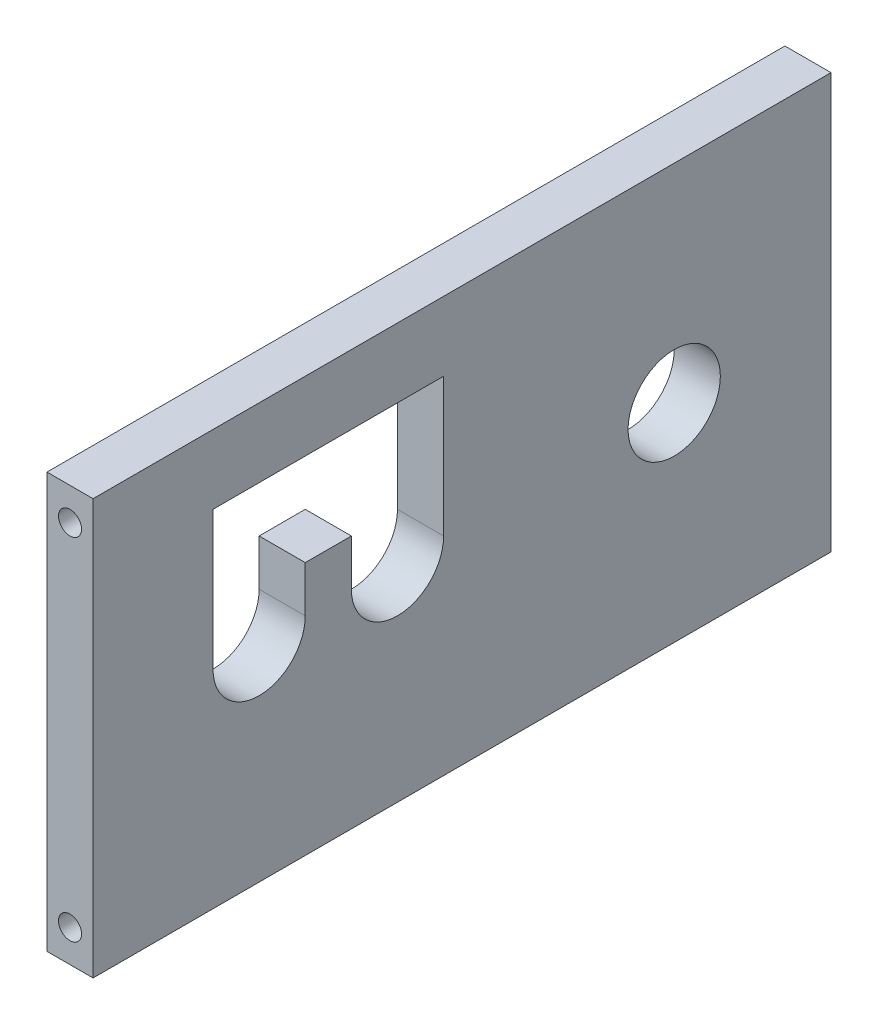
SolidWorks part; units mm, degrees
ref_plane "前视基准面" through (0, 0, 0) normal (0, 0, 1) x (1, 0, 0)
ref_plane "上视基准面" through (0, 0, 0) normal (0, 1, 0) x (1, 0, 0)
ref_plane "右视基准面" through (0, 0, 0) normal (1, 0, 0) x (0, 0, -1)
sketch "草图2" plane through (0, 0, 0) normal (1, 0, 0) x (0, 0, -1)
  line L1 (-40, 22.5) -> (40, 22.5)
  line L2 (-40, 22.5) -> (-40, -22.5)
  line L3 (-40, -22.5) -> (40, -22.5)
  line L4 (40, 22.5) -> (40, -22.5)
  line L5 (0, -22.5) -> (0, 22.5) construction
  line L6 (-40, 0) -> (40, 0) construction
  circle A0 centre (-10, 0) radius 8.7762
  circle A1 centre (20, 0) radius 9.4656
  point P0 (0, 0)
  dimension "D1" = 80
  dimension "D2" = 45
  dimension "D3" = 30
  dimension "D4" = 20
extrude "凸台-拉伸2" add sketch "草图2" against normal blind 5 contours L1 L4 L3 L2
sketch "草图5" plane through (0, 0, 0) normal (1, 0, 0) x (0, 0, -1)
  line L0 (40, 22.5) -> (40, -22.5) construction
  circle A0 centre (-7, 0) radius 5
  circle A1 centre (23, 0) radius 5
  circle A2 centre (-22, 0) radius 5
  point P10 (-27.7203, 2.1595)
  dimension "D1" = 10
  dimension "D2" = 10
  dimension "D5" = 10
  dimension "D3" = 30
  dimension "D4" = 17
  dimension "D6" = 15
ref_axis "基准轴2" through (0, 0, 0) along (0, 0, -1)
ref_plane "基准面5" through (0, 0, 0) normal (0, -1, 0) x (0, 0, -1)
hole_wizard "M3 螺纹孔1" positions "草图11" profile "草图12" tap size "M3" standard "GB"
sketch "草图11" plane through (0, 0, 40) normal (0, 0, 1) x (1, 0, 0)
  line L0 (-5, 22.5) -> (0, 22.5) construction
  line L1 (0, 22.5) -> (0, -22.5) construction
  line L2 (-5, -22.5) -> (0, -22.5) construction
  point P0 (-2.5, 19)
  point P2 (-2.5, -19)
  dimension "D1" = 3.5
  dimension "D2" = 2.5
  dimension "D3" = 3.5
  dimension "D4" = 2.5
sketch "草图12" plane through (-2.5, 19, 40) normal (1, 0, 0) x (0, -1, 0)
  line L0 (0, 0) -> (0, 8.2511)
  line L1 (0, 8.2511) -> (1.25, 7.5)
  line L2 (1.25, 7.5) -> (1.25, 0)
  line L5 (1.25, 0) -> (0, 0)
  line L10 (0, 8.2511) -> (-1.25, 7.5) construction
  line L11 (0, -6.35) -> (0, 107.95) construction
  dimension "螺纹孔钻头直径" = 2.5
  dimension "螺纹孔钻头深度" = 7.5
  dimension "导头角度" = 118
cosmetic thread "孔螺蚊线1" parameters "D1"=6, "D2"=3
cosmetic thread "孔螺蚊线2" parameters "D1"=6, "D2"=3
ref_axis "基准轴3" through (0, 0, 0) along (0, -1, 0)
ref_plane "基准面7" through (0, 0, 0) normal (0, 0, 1) x (0, -1, 0)
mirror "镜向1" about plane through (0, 0, 0) normal (0, 0, 1) of "M3 螺纹孔1"
extrude "切除-拉伸1" cut sketch "草图5" against normal blind 10
sketch "草图13" plane through (0, 0, 0) normal (1, 0, 0) x (0, 0, -1)
  line L0 (-27, 0) -> (-27, 15)
  line L1 (-24.75, 0) -> (24.75, 0) construction
  line L2 (-27, 15) -> (-13.3408, 15)
  line L3 (-13.3408, 15) -> (-4.2268, 15)
  line L4 (-4.2268, 15) -> (-2, 15)
  line L5 (-2, 0) -> (-2, 15)
  line L6 (-12, 0) -> (-12, 5)
  line L7 (-17, 0) -> (-17, 5)
  line L8 (-12, 5) -> (-17, 5)
  line L9 (-27, 0) -> (-17, 0)
  line L10 (-12, 0) -> (-2, 0)
  circle A0 centre (-22, 0) radius 5 construction
  circle A1 centre (-7, 0) radius 5 construction
  dimension "D1" = 15
  dimension "D2" = 10
extrude "切除-拉伸2" cut sketch "草图13" against normal blind 10
